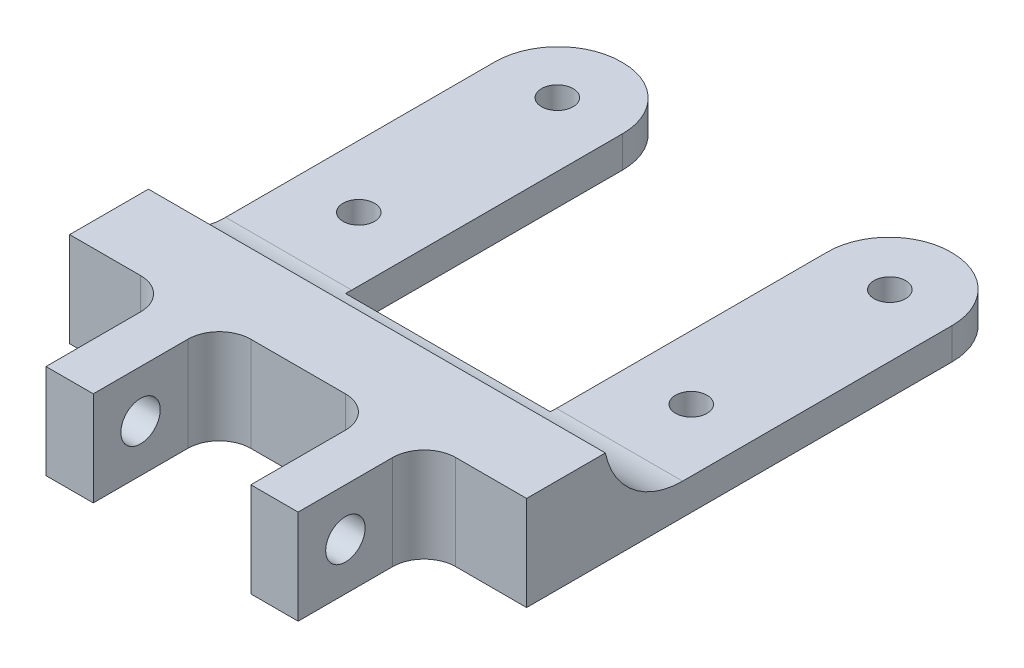
SolidWorks part; units mm, degrees
ref_plane "Front Plane" through (0, 0, 0) normal (0, 0, 1) x (1, 0, 0)
ref_plane "Top Plane" through (0, 0, 0) normal (0, 1, 0) x (1, 0, 0)
ref_plane "Right Plane" through (0, 0, 0) normal (1, 0, 0) x (0, 0, -1)
sketch "Sketch1" plane through (0, 0, 0) normal (0, 1, 0) x (1, 0, 0)
  line L0 (24.9, 26) -> (25, 26)
  line L1 (0, 0) -> (29, 0)
  line L2 (0, 0) -> (0, 22)
  line L3 (4, 26) -> (4.1, 26)
  line L4 (29, 0) -> (29, 22)
  line L6 (8, 22.1) -> (8, 4.5)
  line L7 (8, 4.5) -> (21, 4.5)
  line L8 (21, 22.1) -> (21, 4.5)
  circle A0 centre (3.95, 22) radius 1
  circle A1 centre (25.05, 22) radius 1
  circle A2 centre (25.05, 9.4) radius 1
  circle A3 centre (3.95, 9.4) radius 1
  arc A4 (0, 22) -> (4, 26) centre (4, 22) cw
  arc A5 (25, 26) -> (29, 22) centre (25, 22) cw
  arc A6 (24.9, 26) -> (21, 22.1) centre (24.9, 22.1) ccw
  arc A7 (4.1, 26) -> (8, 22.1) centre (4.1, 22.1) cw
  point P19 (0, 26)
  point P22 (29, 26)
  point P23 (0, 0)
  dimension "D7" = 2
  dimension "D8" = 2
  dimension "D9" = 2
  dimension "D10" = 2
  dimension "D18" = 4
  dimension "D19" = 3.9
  dimension "D1" = 29
  dimension "D2" = 26
  dimension "D3" = 21.1
  dimension "D4" = 3.95
  dimension "D5" = 21.1
  dimension "D6" = 3.95
  dimension "D11" = 9.4
  dimension "D12" = 9.4
  dimension "D13" = 12.6
  dimension "D14" = 12.6
  dimension "D15" = 8
  dimension "D16" = 8
  dimension "D17" = 4.5
extrude "Boss-Extrude1" add sketch "Sketch1" along normal blind 2 contours L3 L8 L7 L6 L2 L1 L4 A3 A2 A1 A0 region at (24.95, 0, -25.6105)
sketch "Sketch2" plane through (0, 2, 0) normal (0, 1, 0) x (1, 0, 0)
  line L1 (0, 0) -> (29, 0)
  line L2 (0, 0) -> (0, -5)
  line L3 (0, -5) -> (29, -5)
  line L4 (29, 0) -> (29, -5)
  dimension "D1" = 5
extrude "Boss-Extrude2" add sketch "Sketch2" along normal blind 4 and the other way blind 2
fillet "Fillet1" radius 5 1 edges at (14.5, 2, 0)
sketch "Sketch3" plane through (0, 0, 5) normal (0, 0, 1) x (1, 0, 0)
  line L0 (0, 6) -> (29, 6) construction
  line L1 (9.5, 6) -> (6.5, 6)
  line L2 (9.5, 6) -> (9.5, 0)
  line L3 (9.5, 0) -> (6.5, 0)
  line L4 (6.5, 6) -> (6.5, 0)
  line L5 (0, 0) -> (29, 0) construction
  line L7 (0, 0) -> (0, 6) construction
  line L8 (29, 0) -> (29, 6) construction
  line L9 (19.5, 0) -> (22.5, 0)
  line L10 (19.5, 0) -> (19.5, 6)
  line L11 (19.5, 6) -> (22.5, 6)
  line L12 (22.5, 0) -> (22.5, 6)
  dimension "D1" = 3
  dimension "D2" = 6.5
  dimension "D3" = 6.5
  dimension "D4" = 3
extrude "Boss-Extrude3" add sketch "Sketch3" along normal blind 8
fillet "Fillet2" radius 2 4 edges at (9.5, 3, 5) (6.5, 3, 5) (19.5, 3, 5) (22.5, 3, 5)
sketch "Sketch4" plane through (9.5, 0, 0) normal (1, 0, 0) x (0, 0, -1)
  line L0 (-13, 6) -> (-7, 6) construction
  line L1 (-7, 0) -> (-7, 6) construction
  circle A0 centre (-10, 3) radius 1.25
  dimension "D3" = 2.5
  dimension "D1" = 3
  dimension "D2" = 3
extrude "Cut-Extrude1" cut sketch "Sketch4" against normal blind 7 and the other way blind 15
